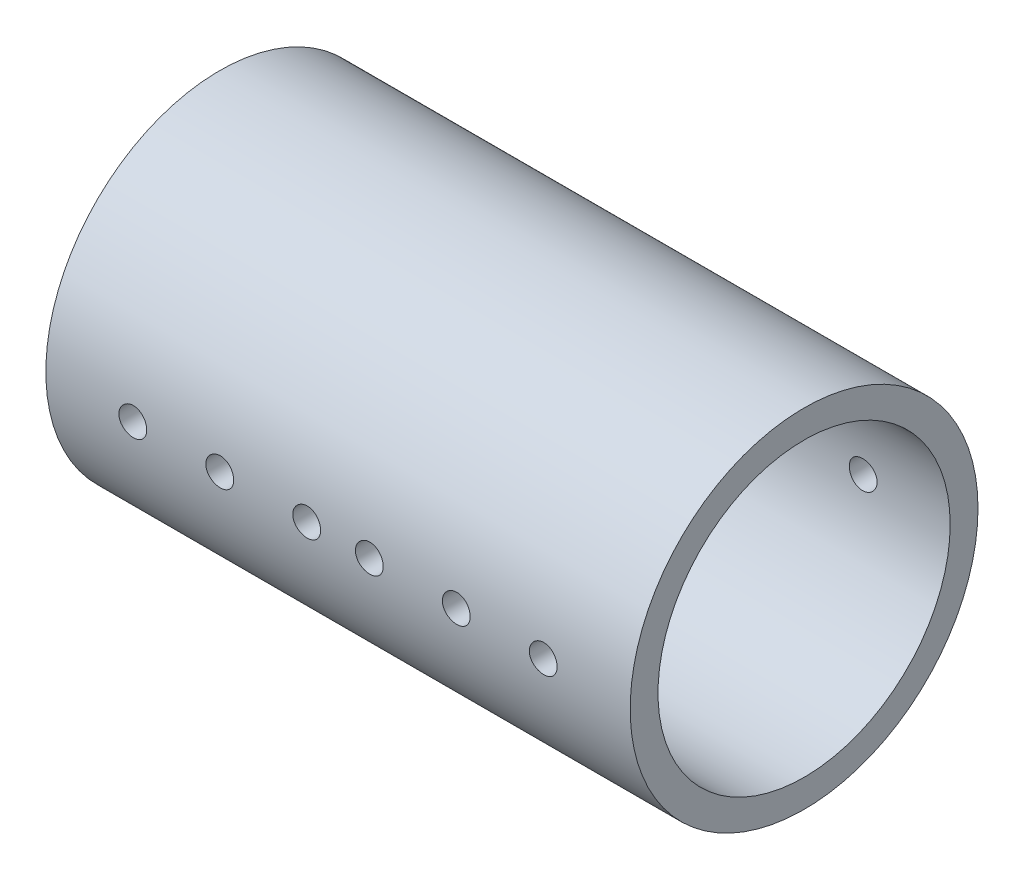
SolidWorks part; units mm, degrees
material "Zoltek Panex 33"
ref_plane "Спереди" through (0, 0, 0) normal (0, 0, 1) x (1, 0, 0)
ref_plane "Сверху" through (0, 0, 0) normal (0, 1, 0) x (1, 0, 0)
ref_plane "Справа" through (0, 0, 0) normal (1, 0, 0) x (0, 0, -1)
other "Configuration Table"
sketch "Эскиз2" plane through (0, 0, 0) normal (1, 0, 0) x (0, 0, -1)
  circle A0 centre (0, 0) radius 25
  circle A1 centre (0, 0) radius 21
  dimension "D1" = 50
  dimension "D2" = 42
extrude "Бобышка-Вытянуть2" add sketch "Эскиз2" along normal blind 84
ref_plane "Плоскость1" through (0, 0, 25) normal (0, 0, 1) x (1, 0, 0)
sketch "Эскиз4" plane through (0, 0, 25) normal (0, 0, 1) x (1, 0, 0)
  line L0 (0, -25) -> (84, -25) construction
  line L1 (84, -25) -> (84, 25) construction
  circle A0 centre (12.5, 0) radius 2
  circle A1 centre (71.5, 0) radius 2
  circle A2 centre (25, 0) radius 2
  circle A3 centre (37.5, 0) radius 2
  circle A4 centre (59, 0) radius 2
  circle A5 centre (46.5, 0) radius 2
  dimension "D1" = 4
  dimension "D4" = 4
  dimension "D6" = 4
  dimension "D8" = 4
  dimension "D10" = 4
  dimension "D11" = 4
  dimension "D2" = 12.5
  dimension "D3" = 25
  dimension "D5" = 12.5
  dimension "D7" = 12.5
  dimension "D9" = 12.5
  dimension "15" = 12.5
  dimension "D12" = 12.5
extrude "Вырез-Вытянуть2" cut sketch "Эскиз4" against normal through all and the other way blind 10 contours A0 | A1 | A2 | A3 | A5 | A4
equation "\"Diameter\"= 50мм"
equation "\"D1@Эскиз2\"= \"Diameter\""
equation "\"Length\" = 84мм"
equation "\"Thickness\"= 4мм"
equation "\"D1@Бобышка-Вытянуть2\"= \"Length\""
equation "\"D2@Эскиз2\" = \"Diameter\" - \"Thickness\" * 2"
equation "\"D4@Эскиз4\"=\"D1@Эскиз4\""
equation "\"D5@Эскиз4\"=\"D2@Эскиз4\""
equation "\"D3@Эскиз4\"=\"Diameter\"/2"
equation "\"D6@Эскиз4\"=\"D1@Эскиз4\""
equation "\"D8@Эскиз4\"=\"D6@Эскиз4\""
equation "\"D10@Эскиз4\"=\"D4@Эскиз4\""
equation "\"D11@Эскиз4\"=\"D4@Эскиз4\""
equation "\"D9@Эскиз4\"=\"D7@Эскиз4\""
